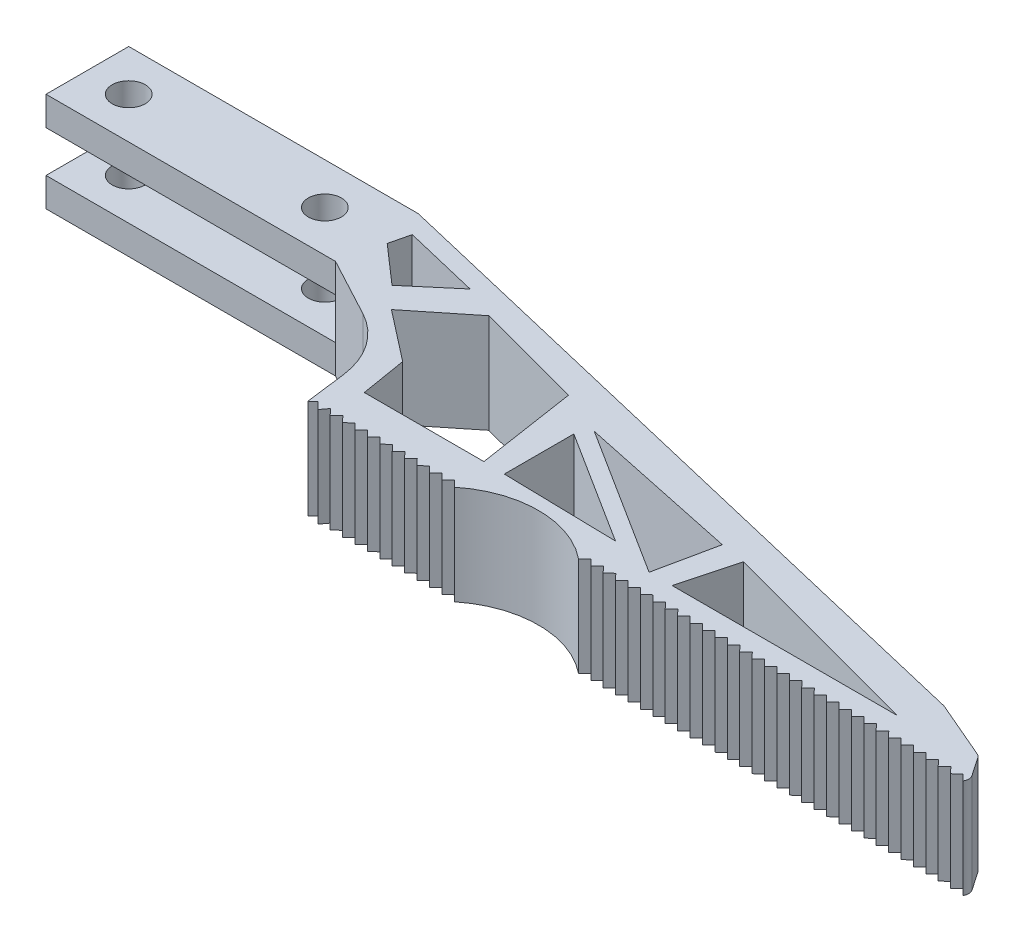
SolidWorks part; units mm, degrees
ref_plane "Front Plane" through (0, 0, 0) normal (0, 0, 1) x (1, 0, 0)
ref_plane "Top Plane" through (0, 0, 0) normal (0, 1, 0) x (1, 0, 0)
ref_plane "Right Plane" through (0, 0, 0) normal (1, 0, 0) x (0, 0, -1)
sketch "Sketch1" plane through (0, 0, 0) normal (0, 1, 0) x (1, 0, 0)
  line L0 (17.5, -5) -> (29.1817, -11.2584)
  line L1 (-17.5, 5) -> (17.5, 5)
  line L2 (-17.5, 5) -> (-17.5, -5)
  line L3 (-17.5, -5) -> (17.5, -5)
  line L4 (17.5, 5) -> (17.5, -5)
  line L5 (-17.5, 5) -> (17.5, -5) construction
  line L6 (-17.5, -5) -> (17.5, 5) construction
  line L7 (29.1817, -11.2584) -> (30.4666, -21.3141)
  line L8 (17.5, 5) -> (100.8163, -14.7574)
  line L9 (30.4666, -21.3141) -> (31.0913, -20.7099)
  line L10 (31.0913, -20.7099) -> (31.9412, -21.5887)
  line L11 (32.5913, -20.7099) -> (33.3163, -21.4595)
  line L12 (31.9412, -21.5887) -> (32.5913, -20.7099)
  line L13 (34.0913, -20.7099) -> (34.8163, -21.4595)
  line L14 (33.3163, -21.4595) -> (34.0913, -20.7099)
  line L15 (35.5913, -20.7099) -> (36.3163, -21.4595)
  line L16 (34.8163, -21.4595) -> (35.5913, -20.7099)
  line L17 (37.0913, -20.7099) -> (37.8163, -21.4595)
  line L18 (36.3163, -21.4595) -> (37.0913, -20.7099)
  line L19 (38.5913, -20.7099) -> (39.3163, -21.4595)
  line L20 (37.8163, -21.4595) -> (38.5913, -20.7099)
  line L21 (40.0913, -20.7099) -> (40.8163, -21.4595)
  line L22 (39.3163, -21.4595) -> (40.0913, -20.7099)
  line L23 (41.5913, -20.7099) -> (42.3163, -21.4595)
  line L24 (40.8163, -21.4595) -> (41.5913, -20.7099)
  line L25 (43.0913, -20.7099) -> (43.8163, -21.4595)
  line L26 (42.3163, -21.4595) -> (43.0913, -20.7099)
  line L27 (44.5913, -20.7099) -> (45.3163, -21.4595)
  line L28 (43.8163, -21.4595) -> (44.5913, -20.7099)
  line L29 (46.0913, -20.7099) -> (46.8163, -21.4595)
  line L30 (45.3163, -21.4595) -> (46.0913, -20.7099)
  line L31 (64.0913, -20.7099) -> (63.3417, -21.4595)
  line L32 (46.8163, -21.4595) -> (47.5913, -20.7099)
  line L33 (47.5913, -20.7099) -> (48.3163, -21.4595)
  line L34 (100.8163, -14.7574) -> (108.108, -17.8885)
  line L35 (108.108, -17.8885) -> (110.5533, -21.4595)
  line L36 (101.5913, -20.7099) -> (102.3163, -21.4595)
  line L37 (110.5533, -21.4595) -> (100.8163, -21.4595)
  line L38 (100.8163, -21.4595) -> (101.5913, -20.7099)
  line L39 (103.0913, -20.7099) -> (103.8163, -21.4595)
  line L40 (102.3163, -21.4595) -> (103.0913, -20.7099)
  line L41 (104.5913, -20.7099) -> (105.3163, -21.4595)
  line L42 (103.8163, -21.4595) -> (104.5913, -20.7099)
  line L43 (106.0913, -20.7099) -> (106.8163, -21.4595)
  line L44 (105.3163, -21.4595) -> (106.0913, -20.7099)
  line L45 (107.5913, -20.7099) -> (108.3163, -21.4595)
  line L46 (106.8163, -21.4595) -> (107.5913, -20.7099)
  line L47 (109.0913, -20.7099) -> (109.8163, -21.4595)
  line L48 (108.3163, -21.4595) -> (109.0913, -20.7099)
  line L53 (64.0913, -20.7099) -> (64.8163, -21.4595)
  line L55 (65.5913, -20.7099) -> (66.3163, -21.4595)
  line L56 (64.8163, -21.4595) -> (65.5913, -20.7099)
  line L57 (67.0913, -20.7099) -> (67.8163, -21.4595)
  line L58 (66.3163, -21.4595) -> (67.0913, -20.7099)
  line L59 (68.5913, -20.7099) -> (69.3163, -21.4595)
  line L60 (67.8163, -21.4595) -> (68.5913, -20.7099)
  line L61 (70.0913, -20.7099) -> (70.8163, -21.4595)
  line L62 (69.3163, -21.4595) -> (70.0913, -20.7099)
  line L63 (71.5913, -20.7099) -> (72.3163, -21.4595)
  line L64 (70.8163, -21.4595) -> (71.5913, -20.7099)
  line L65 (73.0913, -20.7099) -> (73.8163, -21.4595)
  line L66 (72.3163, -21.4595) -> (73.0913, -20.7099)
  line L67 (74.5913, -20.7099) -> (75.3163, -21.4595)
  line L68 (73.8163, -21.4595) -> (74.5913, -20.7099)
  line L69 (76.0913, -20.7099) -> (76.8163, -21.4595)
  line L70 (75.3163, -21.4595) -> (76.0913, -20.7099)
  line L71 (77.5913, -20.7099) -> (78.3163, -21.4595)
  line L72 (76.8163, -21.4595) -> (77.5913, -20.7099)
  line L73 (79.0913, -20.7099) -> (79.8163, -21.4595)
  line L74 (78.3163, -21.4595) -> (79.0913, -20.7099)
  line L75 (80.5913, -20.7099) -> (81.3163, -21.4595)
  line L76 (79.8163, -21.4595) -> (80.5913, -20.7099)
  line L77 (82.0913, -20.7099) -> (82.8163, -21.4595)
  line L78 (81.3163, -21.4595) -> (82.0913, -20.7099)
  line L79 (83.5913, -20.7099) -> (84.3163, -21.4595)
  line L80 (82.8163, -21.4595) -> (83.5913, -20.7099)
  line L81 (85.0913, -20.7099) -> (85.8163, -21.4595)
  line L82 (84.3163, -21.4595) -> (85.0913, -20.7099)
  line L83 (86.5913, -20.7099) -> (87.3163, -21.4595)
  line L84 (85.8163, -21.4595) -> (86.5913, -20.7099)
  line L85 (88.0913, -20.7099) -> (88.8163, -21.4595)
  line L86 (87.3163, -21.4595) -> (88.0913, -20.7099)
  line L87 (89.5913, -20.7099) -> (90.3163, -21.4595)
  line L88 (88.8163, -21.4595) -> (89.5913, -20.7099)
  line L89 (91.0913, -20.7099) -> (91.8163, -21.4595)
  line L90 (90.3163, -21.4595) -> (91.0913, -20.7099)
  line L91 (92.5913, -20.7099) -> (93.3163, -21.4595)
  line L92 (91.8163, -21.4595) -> (92.5913, -20.7099)
  line L93 (94.0913, -20.7099) -> (94.8163, -21.4595)
  line L94 (93.3163, -21.4595) -> (94.0913, -20.7099)
  line L95 (95.5913, -20.7099) -> (96.3163, -21.4595)
  line L96 (94.8163, -21.4595) -> (95.5913, -20.7099)
  line L97 (97.0913, -20.7099) -> (97.8163, -21.4595)
  line L98 (96.3163, -21.4595) -> (97.0913, -20.7099)
  line L99 (98.5913, -20.7099) -> (99.3163, -21.4595)
  line L100 (97.8163, -21.4595) -> (98.5913, -20.7099)
  line L101 (100.0913, -20.7099) -> (100.8163, -21.4595)
  line L102 (99.3163, -21.4595) -> (100.0913, -20.7099)
  circle A0 centre (-12.5, 0) radius 2
  circle A1 centre (11.21, 0) radius 2
  arc A2 (48.3163, -21.4595) -> (63.3417, -21.4595) centre (55.829, -30.7283) cw
  point P0 (0, 0)
  dimension "D5" = 4
  dimension "D6" = 4
  dimension "D7" = 7
  dimension "D1" = 35
  dimension "D2" = 10
  dimension "D3" = 23.71
  dimension "D4" = 5
  dimension "D9" = 1.5
extrude "Boss-Extrude1" add sketch "Sketch1" along normal blind 12 contours L4 | L4 L1 L2 L3 A1 A0 region at (55.9009, 0, 11.7058) region at (0.0499, 0, 0)
sketch "Sketch4" plane through (0, 0, 5) normal (0, 0, 1) x (1, 0, 0)
  line L0 (17.5, 12) -> (17.5, 0) construction
  line L1 (-17.5, 8.5) -> (17.5, 8.5)
  line L2 (-17.5, 8.5) -> (-17.5, 3.5)
  line L3 (-17.5, 3.5) -> (17.5, 3.5)
  line L4 (17.5, 8.5) -> (17.5, 3.5)
  line L5 (-17.5, 8.5) -> (17.5, 3.5) construction
  line L6 (-17.5, 3.5) -> (17.5, 8.5) construction
  line L7 (-17.5, 12) -> (17.5, 12) construction
  line L8 (-17.5, 12) -> (-17.5, 0) construction
  line L9 (0, 12) -> (0, -0.2997) construction
  line L10 (-17.5, 6) -> (17.5, 6) construction
  point P0 (0, 6)
  dimension "D1" = 5
extrude "Cut-Extrude1" cut sketch "Sketch4" against normal through all
fillet "Fillet2" radius 10 1 edges at (29.1817, 6, 11.2584)
fillet "Fillet3" radius 1 3 edges at (100.8163, 6, 14.7574) (108.108, 6, 17.8885) (110.5533, 6, 21.4595)
sketch "Sketch5" plane through (0, 12, 0) normal (0, 1, 0) x (1, 0, 0)
  line L10 (19.3321, 2.4424) -> (28.5268, 0.2422)
  line L11 (19.3321, 2.4424) -> (18.7476, 0)
  line L12 (18.7476, 0) -> (23.4154, -4.0879)
  line L13 (23.4154, -4.0879) -> (28.5268, 0.2422)
  line L14 (25.9211, -6.6618) -> (32.046, -11.4286)
  line L15 (32.046, -11.4286) -> (32.9675, -16.9884)
  line L16 (32.9675, -16.9884) -> (47.4245, -16.9884)
  line L17 (47.4245, -16.9884) -> (45.5904, -4.9347)
  line L18 (45.5904, -4.9347) -> (32.4549, -1.4215)
  line L19 (32.4549, -1.4215) -> (25.9211, -6.6618)
  line L20 (50.9353, -7.1517) -> (70.5378, -11.2822)
  line L21 (70.5378, -11.2822) -> (68.9979, -18.5904)
  line L22 (68.9979, -18.5904) -> (50.9353, -7.1517)
  line L23 (49.9673, -8.6621) -> (63.7011, -17.3596)
  line L24 (63.7011, -17.3596) -> (49.9673, -17.0617)
  line L25 (49.9673, -17.0617) -> (49.9673, -8.6621)
  line L26 (71.7721, -18.5904) -> (98.9778, -18.5904)
  line L27 (98.9778, -18.5904) -> (73.6008, -11.7782)
  line L30 (19.3321, 2.4424) -> (100.1657, -16.8762) construction
  line L31 (73.6008, -11.7782) -> (71.7721, -18.5904)
  point P1 (73.1883, -19.1241)
  point P17 (50.3385, -16.8762)
  point P21 (64.0723, -17.174)
extrude "Cut-Extrude2" cut sketch "Sketch5" against normal blind 12
